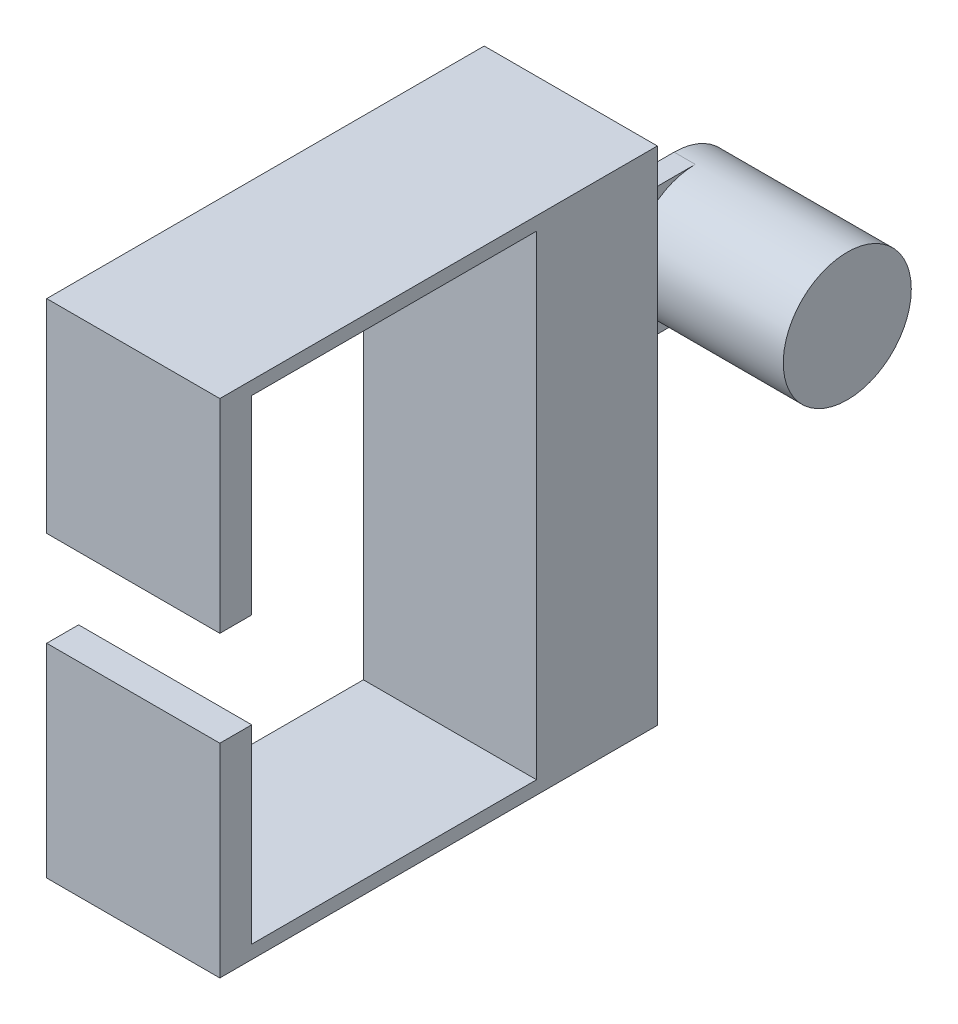
SolidWorks part; units mm, degrees
material "6061-T6 (SS)"
ref_plane "Front Plane" through (0, 0, 0) normal (1, 0, 0) x (0, 1, 0)
ref_plane "Top Plane" through (0, 0, 0) normal (0, 0, 1) x (0, 1, 0)
ref_plane "Right Plane" through (0, 0, 0) normal (0, 1, 0) x (-1, 0, 0)
sketch "Sketch1" plane through (0, 0, 0) normal (1, 0, 0) x (0, 1, 0)
  line L0 (0, 0) -> (0, 83.9097) construction
  line L1 (6.3602, 83.9097) -> (-6.3602, 83.9097) construction
  line L2 (-6.3602, 83.9097) -> (-6.3602, 79.6449)
  line L3 (6.3602, 83.9097) -> (6.3602, 79.6449)
  line L4 (-6.3602, 79.6449) -> (-31.7703, 79.6449)
  line L5 (6.3602, 79.6449) -> (31.7703, 79.6449)
  line L6 (-31.7703, 79.6449) -> (-31.7703, 41.5576)
  line L7 (31.7703, 79.6449) -> (31.7703, 41.5576)
  line L8 (-31.7703, 41.5576) -> (31.7703, 41.5576)
  line L9 (-6.3602, 83.9097) -> (-33.5542, 83.9097)
  line L10 (6.3602, 83.9097) -> (33.5542, 83.9097)
  line L11 (-33.5542, 83.9097) -> (-33.5542, 25.4)
  line L12 (33.5542, 83.9097) -> (33.5542, 25.4)
  line L13 (-33.5542, 25.4) -> (-8.5623, 25.4)
  line L14 (33.5542, 25.4) -> (8.5623, 25.4)
  line L15 (-8.5623, 25.4) -> (-8.5623, 0)
  line L16 (8.5623, 25.4) -> (8.5623, 0)
  line L17 (-8.5623, 25.4) -> (8.5623, 25.4)
  circle A0 centre (0, 0) radius 8.5623
  point P12 (0, 41.5576)
  dimension "D1" = 17.1247
  dimension "D2" = 25.4
  dimension "D3" = 16.1576
  dimension "D4" = 12.7203
  dimension "D5" = 38.0873
  dimension "D6" = 63.5406
  dimension "D7" = 1.7839
  dimension "D8" = 4.2649
extrude "Boss-Extrude1" add sketch "Sketch1" along normal blind 20.32 contours A0 region at (0, 0, 0)
extrude "Boss-Extrude2" add sketch "Sketch1<5>" against normal blind 2.8337 contours A0 | A0 L16 L17 L15 region at (0, 0, 15.9646) region at (0, 0, 0)
sketch "Sketch1<5>" plane through (0, 0, 0) normal (1, 0, 0) x (0, 1, 0) same geometry as "Sketch1"
extrude "Boss-Extrude3" add sketch "Sketch1<6>" along normal blind 20.32 and the other way blind 2.8337 contours L13 L17 L14 L12 L10 L3 L5 L7 L8 L6 L4 L2 L9 L11 region at (0, -7.2505, 81.7773)
sketch "Sketch1<6>" plane through (0, 0, 0) normal (1, 0, 0) x (0, 1, 0) same geometry as "Sketch1"
equation "\"dmax\"= 0.005'maximum allowed deflection"
equation "\"Sa\"= 4 'safety factor"
equation "\"p\"= 3.141592654 'mmmmmmm ... pie"
equation "\"f\"= 750 'load"
equation "\"l\"= 0.8 'strap hanger length"
equation "\"lB\"= 1'Strap Hangdown Length"
equation "\"Ta\"= 0.5008'T Slot Max Width A"
equation "\"Tb\"= 1.0004'T slot clearance a"
equation "\"Tc\"= 1.4995'T slot clearance c"
equation "\"s\"= 39885.37799'Yeild Strength"
equation "\"E\"= 10007604'Modulus of Elasticity"
equation "\"dA\"= ( ( \"Sa\" * \"f\" * ( \"l\" / 2 ) * 32 ) / ( \"p\" * \"s\" ) ) ^ ( 1 / 3 )'Feature A diameter"
equation "\"bB\"= \"dA\"'Feature B Width"
equation "\"hB\"= ( \"f\" * \"Sa\" ) / ( \"s\" * \"dA\" )'Feature B depth"
equation "\"OAL\"= \"l\" + \"hB\"'Overall Length"
equation "\"lC\"= \"Ta\" + ( \"Tb\" * 2 )'Feature C Length"
equation "\"hC\"= ( ( \"f\" * ( \"lC\" ^ 3 ) * \"Sa\" ) / ( \"OAL\" * \"E\" * \"dmax\" * 4 ) ) ^ ( 1 / 3 )'Feature C Depth"
equation "\"lD\"= \"hC\" + \"Tc\"'Feature D length"
equation "\"fD\"= \"f\" / 2'Reaction Force at D"
equation "\"hD\"= ( \"fD\" * \"lD\" * \"Sa\" ) / ( \"OAL\" * \"E\" * \"dmax\" )'Feature D depth"
equation "\"wE\"= \"fD\" / \"hD\"'distributed load for E"
equation "\"hE\"= ( ( \"wE\" * ( \"hD\" ^ 2 ) * ( \"Tc\" ^ 2 ) * \"Sa\" ) / ( \"E\" * \"dmax\" ) ) ^ ( 1 / 3 )'Feature E depth"
equation "\"D3@Sketch1\"=\"hC\""
equation "\"D1@Sketch1\"=\"dA\""
equation "\"D2@Sketch1\"=\"lB\""
equation "\"D7@Sketch1\"=\"hD\""
equation "\"D8@Sketch1\"=\"hE\""
equation "\"D4@Sketch1\"=\"Ta\""
equation "\"D5@Sketch1\"=\"Tc\""
equation "\"D1@Boss-Extrude1\"=\"l\""
equation "\"D1@Boss-Extrude2\"=\"hB\""
equation "\"D1@Boss-Extrude3\"=\"l\""
equation "\"D2@Boss-Extrude3\"=\"hB\""
